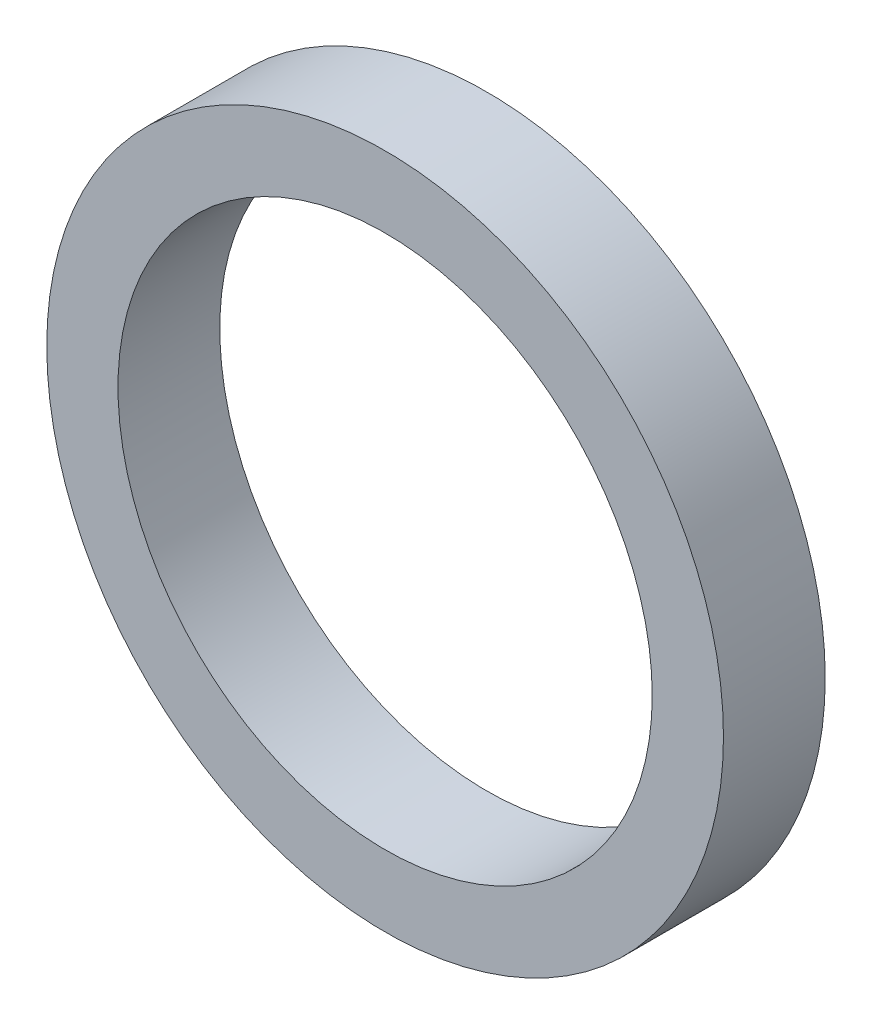
SolidWorks part; units mm, degrees
ref_plane "Front Plane" through (0, 0, 0) normal (0, 0, 1) x (1, 0, 0)
ref_plane "Top Plane" through (0, 0, 0) normal (0, 1, 0) x (1, 0, 0)
ref_plane "Right Plane" through (0, 0, 0) normal (1, 0, 0) x (0, 0, -1)
sketch "Sketch1" plane through (0, 0, 3) normal (0, 0, 1) x (1, 0, 0)
  circle A0 centre (33, 0) radius 2.625
  circle A1 centre (33, 0) radius 3.325
  point P4 (0, 0)
  point P5 (33, 0)
  dimension "D1" = 5.25
  dimension "D2" = 6.65
extrude "Boss-Extrude1" add sketch "Sketch1" along normal blind 1
equation "\"RingPinShaft\"= 5.05"
equation "\"CenterBearingOut\"=32.05"
equation "\"OutputBearingOut\"=37.05"
equation "\"RingPostIn\"=5.15"
equation "\"CamBearingOut\"=15.1"
equation "\"DiskOutputShaft\"=10.1"
equation "\"CenterShaft\"=25.2"
equation "\"Eccentricity\"=2"
equation "\"CycCamShaft\"=10.05"
equation "\"m3Thru\"=3.15"
equation "\"m3Insert\"=4.2"
equation "\"D1@Sketch1\"=\"RingPostIn\"+0.1"
equation "\"D2@Sketch1\"=\"RingPostIn\"+1.5"
